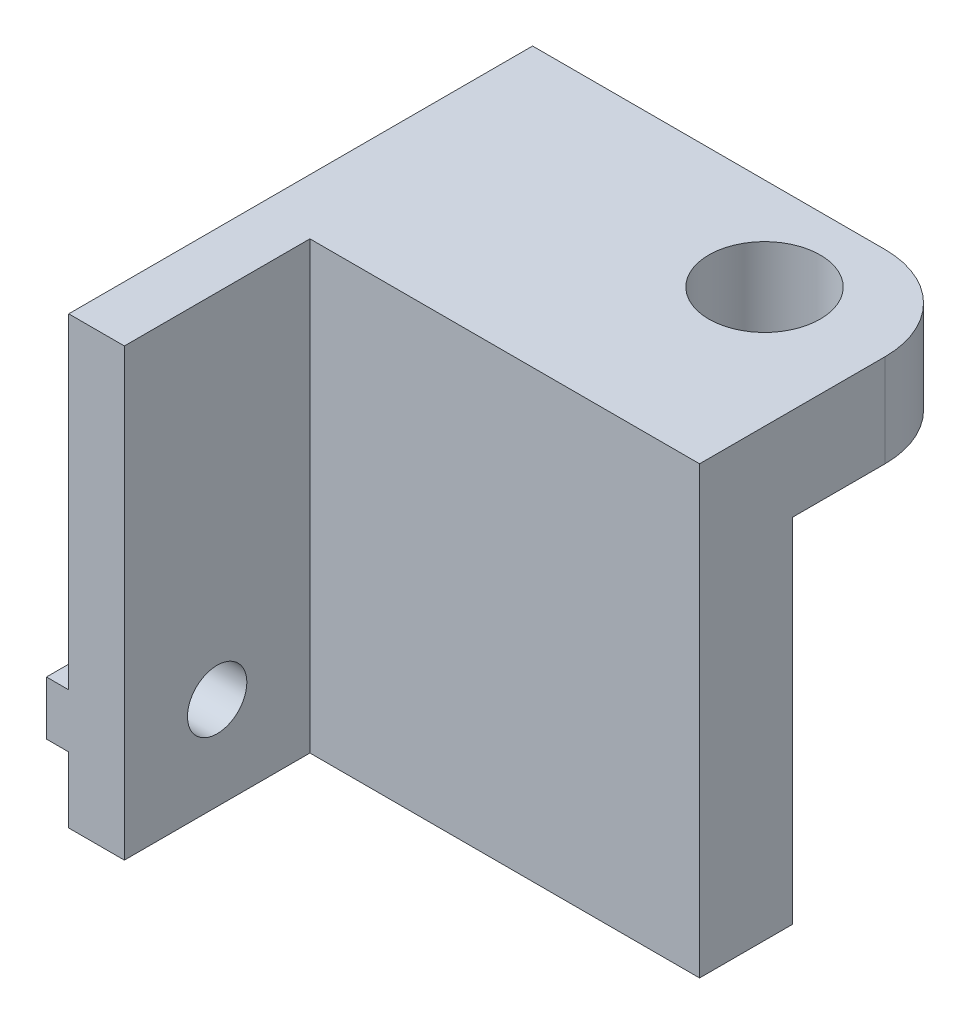
SolidWorks part; units mm, degrees
ref_plane "Front Plane" through (0, 0, 0) normal (0, 0, 1) x (1, 0, 0)
ref_plane "Top Plane" through (0, 0, 0) normal (0, 1, 0) x (1, 0, 0)
ref_plane "Right Plane" through (0, 0, 0) normal (1, 0, 0) x (0, 0, -1)
sketch "Esquisse1" plane through (0, 0, 0) normal (0, 0, 1) x (1, 0, 0)
  line L0 (-12, -5) -> (12, -5)
  line L1 (12, -5) -> (12, -1.45)
  line L2 (12, -1.45) -> (13.2, -1.45)
  line L3 (13.2, -1.45) -> (13.2, 1.45)
  line L4 (13.2, 1.45) -> (12, 1.45)
  line L5 (12, 1.45) -> (12, 19)
  line L6 (12, 19) -> (-12, 19)
  line L7 (-12, 19) -> (-12, -5)
  point P0 (13.2, 0)
  point P11 (0, -5)
  dimension "D1" = 2.9
  dimension "D2" = 1.2
  dimension "D3" = 24
  dimension "D4" = 24
  dimension "D5" = 3.55
extrude "Boss.-Extru.1" add sketch "Esquisse1" along normal blind 25
ref_plane "Plan1" through (9, 0, 0) normal (1, 0, 0) x (0, 0, -1)
sketch "Esquisse2" plane through (9, 0, 0) normal (1, 0, 0) x (0, 0, -1)
  line L0 (0, 1.45) -> (0, 19) construction
  line L1 (-10, 14) -> (0, 14)
  line L2 (-10, 14) -> (-10, 5)
  line L3 (-10, 5) -> (0, 5)
  line L4 (0, 14) -> (0, 5)
  line L5 (-25, 19) -> (0, 19) construction
  line L7 (-25, -5) -> (0, -5) construction
  dimension "D1" = 5
  dimension "D2" = 10
  dimension "D3" = 10
extrude "Enlèv. mat.-Extru.1" cut sketch "Esquisse2" against normal through all
sketch "Esquisse3" plane through (0, 0, 0) normal (0, 0, -1) x (-1, 0, 0)
  line L0 (12, 5) -> (-9, 5) construction
  line L1 (12, 5) -> (-9, 5)
  line L2 (12, 5) -> (12, -5)
  line L3 (12, -5) -> (-9, -5)
  line L4 (-9, 5) -> (-9, -5)
  line L5 (12, 5) -> (12, -5) construction
  line L6 (12, -5) -> (-12, -5) construction
  line L7 (-12, 1.45) -> (-12, 19) construction
  dimension "D1" = 3
extrude "Enlèv. mat.-Extru.2" cut sketch "Esquisse3" against normal up to surface (10 mm away) up to face at (-1.5, 9.5, 10)
sketch "Esquisse4" plane through (0, 19, 0) normal (0, 1, 0) x (1, 0, 0)
  line L0 (12, -25) -> (12, 0) construction
  line L1 (12, 0) -> (-12, 0) construction
  circle A0 centre (-5.5, -5) radius 3
  dimension "D1" = 6
  dimension "D2" = 17.5
  dimension "D3" = 5
extrude "Enlèv. mat.-Extru.3" cut sketch "Esquisse4" against normal through all and the other way through all
sketch "Esquisse5" plane through (13.2, 0, 0) normal (1, 0, 0) x (0, 0, -1)
  line L0 (0, -1.45) -> (0, 1.45) construction
  circle A0 centre (-20, 0) radius 1.6
  point P4 (0, 0)
  dimension "D1" = 3.2
  dimension "D2" = 20
extrude "MakerBeam Fixing Hole" cut sketch "Esquisse5" against normal through all
fillet "Congé2" radius 5 2 edges at (-12, 16.5, 0) (9, 14, 5)
sketch "Esquisse6" plane through (-12, 0, 0) normal (-1, 0, 0) x (0, 0, 1)
  line L0 (25, 19) -> (25, -5) construction
  line L1 (25, -5) -> (15, -5)
  line L2 (25, -5) -> (25, 19)
  line L3 (25, 19) -> (15, 19)
  line L4 (15, -5) -> (15, 19)
  line L5 (25, 19) -> (5, 19) construction
  line L6 (10, 14) -> (10, -5) construction
  line L8 (25, -5) -> (10, -5) construction
  dimension "D1" = 5
extrude "Enlèv. mat.-Extru.4" cut sketch "Esquisse6" against normal up to surface (21 mm away) up to plane "Plan1"
ref_plane "Plan2" through (19, 0, 0) normal (1, 0, 0) x (0, 0, -1)
mirror "Symétrie1" about plane through (19, 0, 0) normal (1, 0, 0) of bodies 106
sketch "Esquisse7" plane through (0, 19, 0) normal (0, 1, 0) x (1, 0, 0)
  line L0 (19, -9.6525) -> (19, 9.6525) construction
  line L1 (19, 0) -> (-12, 0)
  line L2 (19, 0) -> (19, -25)
  line L3 (19, -25) -> (-12, -25)
  line L4 (-12, 0) -> (-12, -25)
  line L7 (12, 0) -> (-7, 0) construction
  line L8 (-12, -15) -> (-12, -5) construction
  line L9 (12, -25) -> (9, -25) construction
  point P8 (-17.6663, -28.78)
extrude "Enlèv. mat.-Extru.5" cut sketch "Esquisse7" against normal through all
